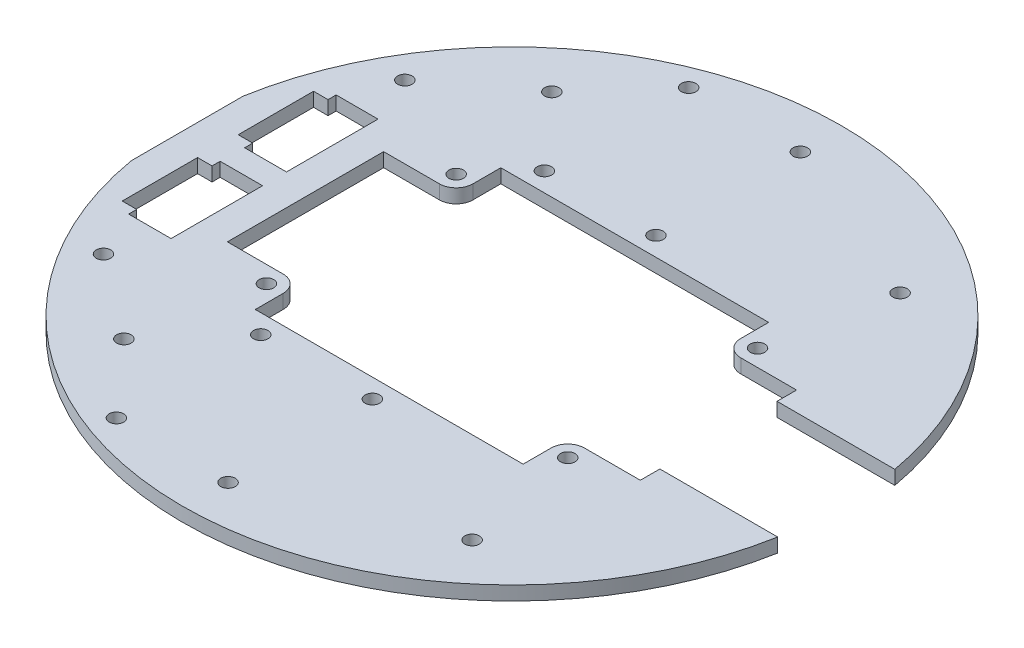
SolidWorks part; units mm, degrees
material "Acrylic (Medium-high impact)"
ref_plane "Front Plane" through (0, 0, 0) normal (0, 0, 1) x (1, 0, 0)
ref_plane "Top Plane" through (0, 0, 0) normal (0, 1, 0) x (1, 0, 0)
ref_plane "Right Plane" through (0, 0, 0) normal (1, 0, 0) x (0, 0, -1)
sketch "Sketch1" plane through (0, 0, 0) normal (0, 1, 0) x (1, 0, 0)
  line L0 (-73.9169, 12.7) -> (-73.9169, -12.7)
  line L1 (-46.99, 0) -> (-73.9169, 0) construction
  line L2 (-34.29, 21.59) -> (34.29, 21.59) construction
  line L3 (34.29, 21.59) -> (34.29, -21.59) construction
  line L4 (34.29, -21.59) -> (-34.29, -21.59) construction
  line L5 (-34.29, -21.59) -> (-34.29, 21.59) construction
  line L6 (0, 21.59) -> (0, 75) construction
  line L7 (34.29, 0) -> (75, 0) construction
  line L8 (0, -25.4) -> (0, -21.59) construction
  line L9 (-34.29, 0) -> (-38.1, 0) construction
  line L10 (-30.48, 27.94) -> (30.48, 27.94)
  line L11 (-30.48, 27.94) -> (-30.48, 21.59)
  line L12 (0, 21.59) -> (0, 27.94) construction
  line L13 (30.48, 27.94) -> (30.48, 21.59)
  line L14 (34.29, 17.78) -> (46.99, 17.78)
  line L15 (-73.9169, 12.7) -> (-73.9169, -12.7) construction
  line L16 (34.29, -17.78) -> (46.99, -17.78)
  line L17 (46.99, 17.78) -> (46.99, -17.78)
  line L18 (-66.9971, -4.5609) -> (-63.6951, -4.5609)
  line L19 (30.48, -21.59) -> (30.48, -27.94)
  line L20 (30.48, -27.94) -> (-30.48, -27.94)
  line L21 (-30.48, -21.59) -> (-30.48, -27.94)
  line L22 (-46.99, -17.78) -> (-34.29, -17.78)
  line L23 (-46.99, -17.78) -> (-46.99, 17.78)
  line L24 (-46.99, 17.78) -> (-34.29, 17.78)
  line L25 (-66.9971, -4.5609) -> (-66.9971, -21.7059)
  line L26 (-66.9971, -21.7059) -> (-63.6951, -21.7059)
  line L27 (-54.04, -4.559) -> (-54.04, -21.7077)
  line L28 (-36.4519, -35.4485) -> (12.0481, -35.4485) construction
  line L29 (12.0481, -35.4485) -> (12.0481, -61.9485) construction
  line L30 (-24.9019, -35.4485) -> (-24.9019, -32.2735) construction
  line L31 (12.0481, -61.9485) -> (-36.4519, -61.9485) construction
  line L32 (-36.4519, -61.9485) -> (-36.4519, -35.4485) construction
  line L35 (-36.4519, -35.4485) -> (-36.4519, -27.94) construction
  line L36 (-12.2019, -35.4485) -> (-12.2019, -61.9485) construction
  line L37 (-63.6951, -4.5609) -> (-63.6951, -2.7212)
  line L38 (-39.6269, -48.6985) -> (-36.4519, -48.6985) construction
  line L39 (-24.9019, -65.1235) -> (-24.9019, -61.9485) construction
  line L40 (-66.867, 21.7077) -> (-63.565, 21.7077)
  line L41 (-66.867, 21.7077) -> (-66.867, 4.5627)
  line L42 (-66.867, 4.5627) -> (-63.565, 4.5627)
  line L43 (-54.04, 21.7077) -> (-54.04, 4.5627)
  line L44 (-63.565, 21.7077) -> (-63.565, 23.5492)
  line L45 (-63.565, 23.5492) -> (-54.04, 23.5492)
  line L46 (-54.04, 23.5492) -> (-54.04, 21.7077)
  line L47 (-63.565, 4.5627) -> (-63.565, 2.7212)
  line L48 (-63.565, 2.7212) -> (-54.04, 2.7212)
  line L49 (-54.04, 2.7212) -> (-54.04, 4.5627)
  line L50 (-63.6951, -2.7212) -> (-54.04, -2.7212)
  line L51 (55.1757, 50.8) -> (55.1757, -50.8) construction
  line L52 (-54.04, -2.7212) -> (-54.04, -4.559)
  line L53 (-63.6951, -21.7059) -> (-63.6951, -23.5455)
  line L54 (-63.6951, -23.5455) -> (-54.04, -23.5455)
  line L55 (-54.04, -23.5455) -> (-54.04, -21.7077)
  line L56 (-54.04, 2.7212) -> (-54.04, -2.7212) construction
  line L57 (-73.9169, 0) -> (-54.04, 0) construction
  arc A0 (-73.9169, -12.7) -> (-73.9169, 12.7) centre (0, 0) ccw
  arc A1 (55.356, -50.6035) -> (55.356, 50.6035) centre (0, 0) ccw construction
  circle A2 centre (-34.29, 21.59) radius 1.651
  circle A3 centre (34.29, 21.59) radius 1.651
  circle A4 centre (-34.29, -21.59) radius 1.651
  circle A5 centre (34.29, -21.59) radius 1.651
  circle A6 centre (-39.6269, 48.6985) radius 1.651 construction
  circle A7 centre (39.6269, -48.6985) radius 1.651
  circle A9 centre (-58.6769, -34.29) radius 1.651
  circle A10 centre (-58.6769, 34.29) radius 1.651
  circle A12 centre (39.6269, 48.6985) radius 1.651
  circle A13 centre (39.6269, -48.6985) radius 1.651 construction
  circle A14 centre (0.4981, -65.1235) radius 1.651
  circle A15 centre (0.4981, -32.2735) radius 1.651
  circle A16 centre (0.4981, 32.2735) radius 1.651
  circle A17 centre (0.4981, 65.1235) radius 1.651
  arc A18 (-34.29, 17.78) -> (-30.48, 21.59) centre (-34.29, 21.59) ccw
  arc A19 (-34.29, -17.78) -> (-30.48, -21.59) centre (-34.29, -21.59) cw
  arc A20 (30.48, 21.59) -> (34.29, 17.78) centre (34.29, 21.59) ccw
  arc A21 (30.48, -21.59) -> (34.29, -17.78) centre (34.29, -21.59) cw
  circle A22 centre (-39.6269, -48.6985) radius 1.651
  circle A23 centre (-24.9019, -32.2735) radius 1.651
  circle A24 centre (-24.9019, -65.1235) radius 1.651
  circle A25 centre (-24.9019, 65.1235) radius 1.651
  circle A26 centre (-39.6269, 48.6985) radius 1.651
  circle A27 centre (-24.9019, 32.2735) radius 1.651
  dimension "D11" = 3.302
  dimension "D1" = 68.58
  dimension "D2" = 43.18
  dimension "D3" = 3.81
  dimension "D4" = 12.7
  dimension "D5" = 60.96
  dimension "D6" = 35.56
  dimension "D7" = 48.5
  dimension "D8" = 26.5
  dimension "D9" = 12.7
  dimension "D10" = 3.175
  dimension "D12" = 17.145
  dimension "D13" = 6.35
  dimension "D14" = 101.6
  dimension "D15" = 3.302
  dimension "D16" = 20.828
  dimension "D17" = 9.525
  dimension "D18" = 1.8415
  dimension "D19" = 1.8377
  dimension "D20" = 17.145
  dimension "D21" = 3.302
  dimension "D22" = 9.6551
  dimension "D23" = 20.8242
extrude "Boss-Extrude1" add sketch "Sketch1" along normal blind 3.175
sketch "Sketch2" plane through (0, 3.175, 0) normal (0, 1, 0) x (1, 0, 0)
  line L0 (46.99, -17.78) -> (46.99, 17.78) construction
  line L1 (46.99, 13.335) -> (73.805, 13.335)
  line L2 (50.3421, 13.335) -> (43.9921, 13.335) construction
  line L3 (46.99, -13.335) -> (73.805, -13.335)
  line L5 (43.9921, -13.335) -> (50.3421, -13.335) construction
  line L6 (46.99, 13.335) -> (46.99, -13.335)
  arc A0 (-73.9169, -12.7) -> (-73.9169, 12.7) centre (0, 0) ccw construction
  arc A1 (73.805, 13.335) -> (73.805, -13.335) centre (0, 0) cw
extrude "Cut-Extrude1" cut sketch "Sketch2" against normal up to surface (3.175 mm away) up to face at (-24.9019, 0, -33.9245)
